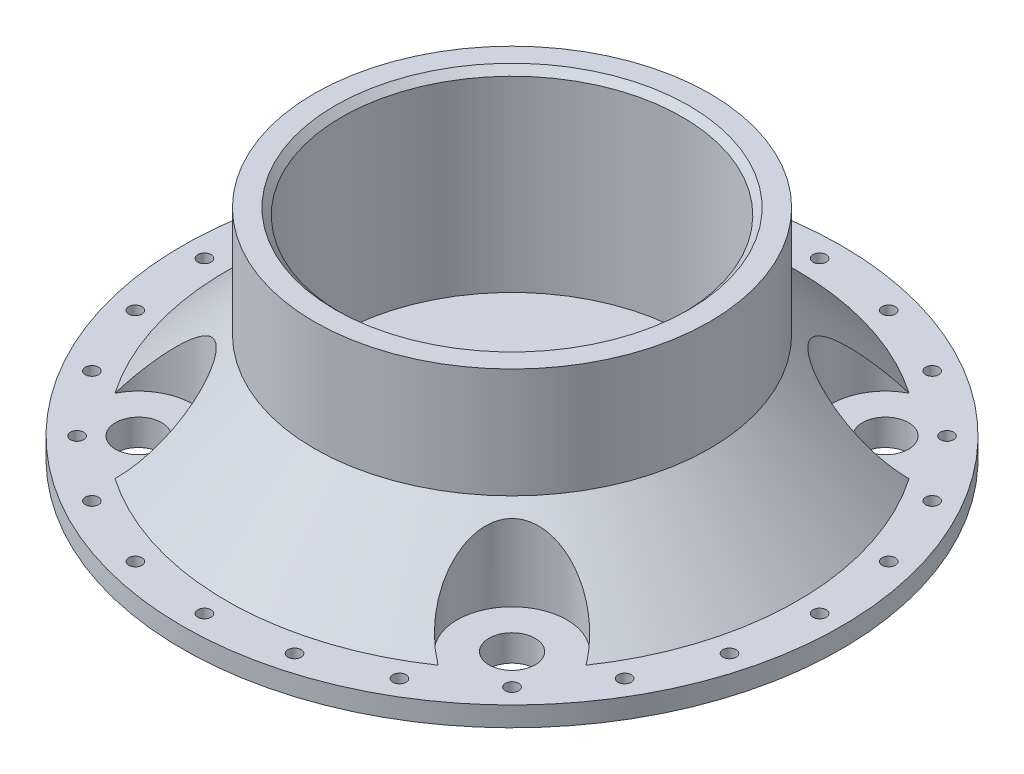
SolidWorks part; units mm, degrees
material "ABS"
ref_plane "Front Plane" through (0, 0, 0) normal (0, 0, 1) x (1, 0, 0)
ref_plane "Top Plane" through (0, 0, 0) normal (0, 1, 0) x (1, 0, 0)
ref_plane "Right Plane" through (0, 0, 0) normal (1, 0, 0) x (0, 0, -1)
sketch "Sketch2" plane through (0, 0, 0) normal (0, 1, 0) x (1, 0, 0)
  circle A0 centre (0, 0) radius 75
  dimension "D1" = 150
extrude "Boss-Extrude1" add sketch "Sketch2" along normal blind 6
sketch "Sketch3" plane through (0, 6, 0) normal (0, 1, 0) x (1, 0, 0)
  circle A0 centre (0, 0) radius 45
  dimension "D1" = 90
extrude "Boss-Extrude2" add sketch "Sketch3" along normal blind 45
sketch "Sketch4" plane through (0, 51, 0) normal (0, 1, 0) x (1, 0, 0)
  circle A0 centre (0, 0) radius 40
  dimension "D1" = 80
extrude "Cut-Extrude1" cut sketch "Sketch4" against normal blind 45
sketch "Sketch7" plane through (0, 6, 0) normal (0, 1, 0) x (1, 0, 0)
  circle A0 centre (0, -70) radius 1.5
  circle A1 centre (0, 0) radius 75 construction
  dimension "D1" = 3
  dimension "D2" = 70
extrude "Cut-Extrude4" cut sketch "Sketch7" against normal through all
pattern_circular "CirPattern2" count 24 over 360 about axis through (0, 6, 0) along (0, 1, 0) of "Cut-Extrude4"
sketch "Sketch8" plane through (0, 6, 0) normal (0, 1, 0) x (1, 0, 0)
  line L1 (-42.5, -42.5) -> (42.5, -42.5)
  line L2 (-42.5, -42.5) -> (-42.5, 42.5)
  line L3 (-42.5, 42.5) -> (42.5, 42.5)
  line L4 (42.5, -42.5) -> (42.5, 42.5)
  line L5 (-42.5, -42.5) -> (42.5, 42.5) construction
  line L6 (-42.5, 42.5) -> (42.5, -42.5) construction
  circle A0 centre (-42.5, 42.5) radius 5.25
  point P0 (0, 0)
  dimension "D3" = 10.5
  dimension "D1" = 85
  dimension "D2" = 85
extrude "Cut-Extrude5" cut sketch "Sketch8" against normal through all contours A0
pattern_linear "LPattern2" count 2 spacing 85 along (1, 0, 0) count 2 spacing 85 along (0, 0, 1) of "Cut-Extrude5"
chamfer "Chamfer2" distance 20 angle 45 1 edges at (0, 6, 45)
sketch "Sketch9" plane through (0, 6, 0) normal (0, 1, 0) x (1, 0, 0)
  circle A0 centre (-42.5, -42.5) radius 12.5
  dimension "D1" = 25
extrude "Cut-Extrude6" cut sketch "Sketch9" along normal through all
mirror "Mirror1" about plane through (0, 0, 0) normal (1, 0, 0) of "Cut-Extrude6" second plane through (0, 0, 0) second plane normal (0, 0, 1)
sketch "Sketch10" plane through (0, 6, 0) normal (0, 1, 0) x (1, 0, 0)
  circle A0 centre (0, 0) radius 40
sketch "Sketch14" plane through (0, 0, 0) normal (0, -1, 0) x (-1, 0, 0)
  circle A0 centre (0, 0) radius 68.5
  circle A1 centre (0, 0) radius 75
extrude "Cut-Extrude8" cut sketch "Sketch14" against normal blind 1.5
sketch "Sketch15" plane through (0, 51, 0) normal (0, 1, 0) x (1, 0, 0)
  circle A0 centre (0, 0) radius 38.75
  circle A2 centre (0, 0) radius 40
  dimension "D1" = 1.25
extrude "Boss-Extrude4" add sketch "Sketch15" against normal blind 1.5
chamfer "Chamfer3" distance 1.5 angle 45 1 edges at (0, 51, 38.75)
